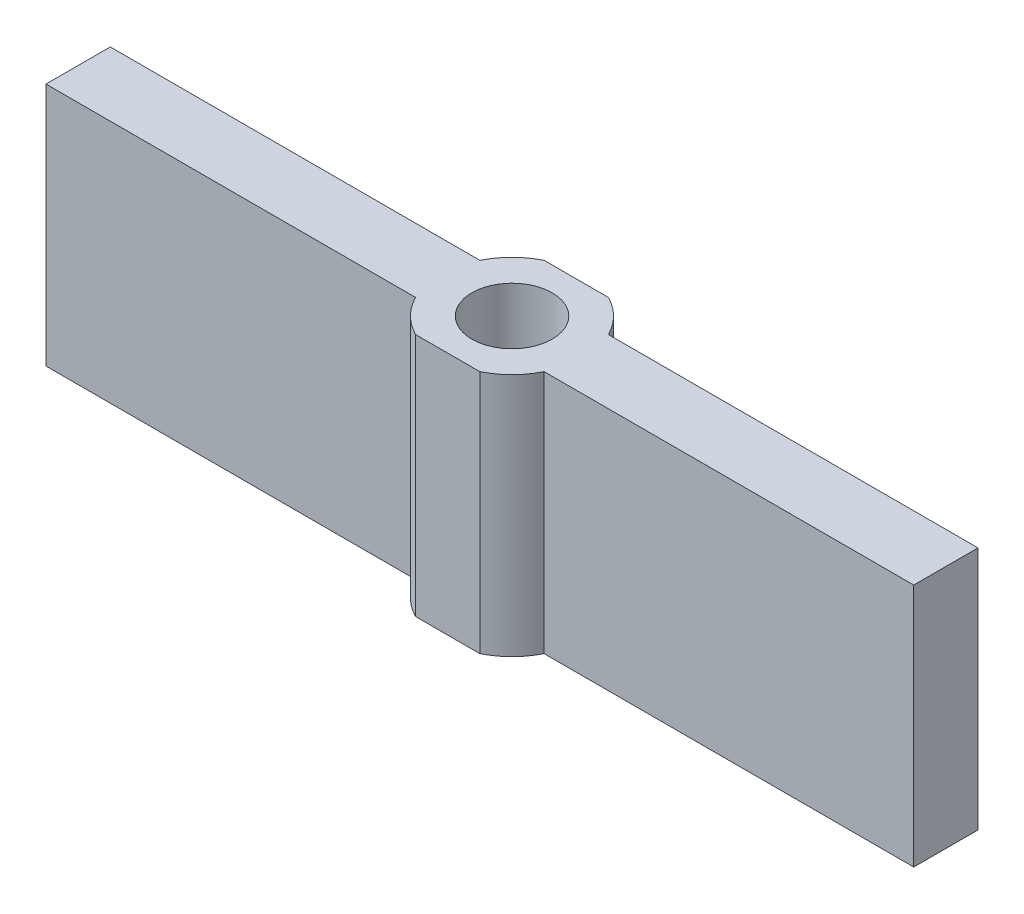
SolidWorks part; units mm, degrees
ref_plane "Front Plane" through (0, 0, 0) normal (0, 0, 1) x (1, 0, 0)
ref_plane "Top Plane" through (0, 0, 0) normal (0, 1, 0) x (1, 0, 0)
ref_plane "Right Plane" through (0, 0, 0) normal (1, 0, 0) x (0, 0, -1)
sketch "Sketch1" plane through (0, 0, 0) normal (0, 0, 1) x (1, 0, 0)
  line L1 (0, 0) -> (27, 0)
  line L2 (0, 0) -> (0, 7.6)
  line L3 (0, 7.6) -> (27, 7.6)
  line L4 (27, 0) -> (27, 7.6)
  line L9 (11.5, 7.6) -> (15.5, 7.6)
  line L10 (11.5, 7.6) -> (11.5, 0)
  line L11 (11.5, 0) -> (15.5, 0)
  line L12 (15.5, 7.6) -> (15.5, 0)
  line L13 (11.5, 7.6) -> (15.5, 0) construction
  line L14 (11.5, 0) -> (15.5, 7.6) construction
  point P5 (13.5, 3.8)
  point P10 (11.5, 3.8)
  point P12 (13.5, 7.6)
  dimension "D3" = 4
  dimension "D1" = 27
  dimension "D2" = 7.6
extrude "Boss-Extrude5" add sketch "Sketch1" along normal blind 1 contours L10 L3 L2 L1 | L3 L12 L1 L4 region at (5.75, 3.8, 0) region at (21.25, 3.8, 0)
extrude "Boss-Extrude6" add sketch "Sketch1<5>" against normal blind 1 contours L3 L12 L1 L4 | L10 L3 L2 L1 region at (5.75, 3.8, 0) region at (21.25, 3.8, 0)
sketch "Sketch1<5>" plane through (0, 0, 0) normal (0, 0, 1) x (1, 0, 0) same geometry as "Sketch1"
extrude "Boss-Extrude7" add sketch "Sketch1<6>" along normal blind 2 and the other way blind 2 contours L12 L3 L10 L1 region at (13.5, 3.8, 0)
sketch "Sketch1<6>" plane through (0, 0, 0) normal (0, 0, 1) x (1, 0, 0) same geometry as "Sketch1"
sketch "Sketch2" plane through (0, 7.6, 0) normal (0, 1, 0) x (1, 0, 0)
  line L1 (11.5, 2) -> (15.5, 2)
  line L2 (11.5, 2) -> (11.5, -2)
  line L3 (11.5, -2) -> (15.5, -2)
  line L4 (15.5, 2) -> (15.5, -2)
  circle A0 centre (13.5, 0) radius 1.25
  circle A1 centre (13.5, 0) radius 2.2361
  point P10 (0, 0)
  point P11 (13.5, 2)
  point P12 (0, 0)
  point P13 (15.5, 0)
  line M2 (11.5, -1) -> (11.5, -2)
  line M3 (11.5, -2) -> (15.5, -2)
  line M4 (15.5, -2) -> (15.5, -1)
  line M8 (15.5, 1) -> (15.5, 2)
  line M9 (15.5, 2) -> (11.5, 2)
  line M10 (11.5, 2) -> (11.5, 1)
extrude "Cut-Extrude1" cut sketch "Sketch2" against normal blind 9 contours A1 M9 M10 | A1 M8 M9 | A1 M3 M4 | A1 M2 M3 | A0 region at (11.796, 7.6, -1.704) region at (15.204, 7.6, -1.704) region at (11.796, 7.6, 1.704) region at (15.204, 7.6, 1.704) region at (13.5, 7.6, 0)
